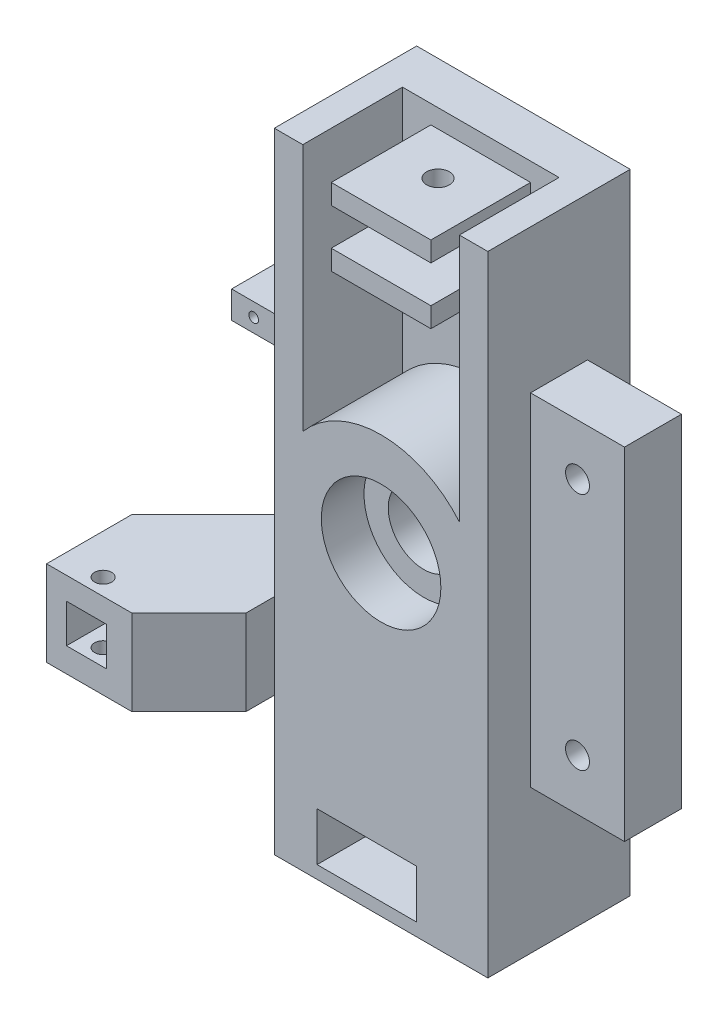
SolidWorks part; units mm, degrees
ref_plane "Front Plane" through (0, 0, 0) normal (0, 0, 1) x (1, 0, 0)
ref_plane "Top Plane" through (0, 0, 0) normal (0, 1, 0) x (1, 0, 0)
ref_plane "Right Plane" through (0, 0, 0) normal (1, 0, 0) x (0, 0, -1)
sketch "Sketch1" plane through (0, 0, 0) normal (0, 1, 0) x (1, 0, 0)
  line L1 (-37.5, -25) -> (37.5, -25)
  line L2 (-37.5, -25) -> (-37.5, 25)
  line L3 (-37.5, 25) -> (37.5, 25)
  line L4 (37.5, -25) -> (37.5, 25)
  line L5 (-37.5, -25) -> (37.5, 25) construction
  line L6 (-37.5, 25) -> (37.5, -25) construction
  point P0 (0, 0)
  dimension "D1" = 50
  dimension "D2" = 75
extrude "BE - main upright body" add sketch "Sketch1" along normal blind 221 contours L3 L4 L1 L2
sketch "Sketch2" plane through (0, 0, 25) normal (0, 0, 1) x (1, 0, 0)
  line L0 (-37.5, 221) -> (37.5, 0) construction
  line L1 (-37.5, 0) -> (37.5, 221) construction
  circle A0 centre (0, 110.5) radius 21
  point P10 (0, 110.5)
  dimension "D1" = 42
sketch "Sketch3" plane through (0, 0, -25) normal (0, 0, -1) x (-1, 0, 0)
  line L0 (-37.5, 0) -> (37.5, 221) construction
  line L1 (-37.5, 221) -> (37.5, 0) construction
  circle A0 centre (0, 110.5) radius 23.5
  point P10 (0, 110.5)
  dimension "D1" = 47
sketch "Sketch4" plane through (0, 0, 25) normal (0, 0, 1) x (1, 0, 0)
  line L0 (-37.5, 221) -> (37.5, 0) construction
  line L1 (37.5, 221) -> (-37.5, 0) construction
  line L2 (-37.5, 0) -> (37.5, 0) construction
  circle A0 centre (0, 110.5) radius 12.5
  dimension "D1" = 25
extrude "CE - Through hole" cut sketch "Sketch4" against normal through all
extrude "CE - Inner bearing" cut sketch "Sketch2" against normal blind 15 contours A0
extrude "CE - Outer bearing" cut sketch "Sketch3" against normal blind 15 contours A0
sketch "Sketch7" plane through (37.5, 0, 0) normal (1, 0, 0) x (0, 0, -1)
  line L0 (25, 221) -> (25, 0) construction
  line L1 (-10, 50.5) -> (10, 50.5)
  line L2 (-10, 50.5) -> (-10, 170.5)
  line L3 (-10, 170.5) -> (10, 170.5)
  line L4 (10, 50.5) -> (10, 170.5)
  line L5 (-10, 50.5) -> (10, 170.5) construction
  line L6 (-10, 170.5) -> (10, 50.5) construction
  line L7 (-25, 110.5) -> (25, 110.5) construction
  line L8 (-25, 221) -> (-25, 0) construction
  point P0 (0, 110.5)
  point P12 (0, 110.5)
  dimension "D1" = 120
  dimension "D2" = 20
extrude "BE - caliper mount" add sketch "Sketch7" along normal blind 33
sketch "Sketch21" plane through (0, 0, 0) normal (0, 0, 1) x (1, 0, 0)
  line L1 (-67.5, 140.0208) -> (-37.5, 140.0208)
  line L2 (-67.5, 140.0208) -> (-67.5, 149.6028)
  line L3 (-67.5, 149.6028) -> (-37.5, 149.6028)
  line L4 (-37.5, 140.0208) -> (-37.5, 149.6028)
  line L5 (-67.5, 140.0208) -> (-37.5, 149.6028) construction
  line L6 (-67.5, 149.6028) -> (-37.5, 140.0208) construction
  line L7 (-37.5, 221) -> (-37.5, 0) construction
  point P0 (-52.5, 144.8118)
  dimension "D1" = 30
extrude "BE - temp sensor mount v2" add sketch "Sketch21" along normal mid plane 20
sketch "Sketch8" [suppressed] plane through (-37.5, 0, 0) normal (-1, 0, 0) x (0, 0, 1)
  line L0 (0, 221) -> (0, 148.4522) construction
  line L1 (-10.7205, 138.4522) -> (10.7205, 138.4522)
  line L2 (-10.7205, 138.4522) -> (-10.7205, 158.4522)
  line L3 (-10.7205, 158.4522) -> (10.7205, 158.4522)
  line L4 (10.7205, 138.4522) -> (10.7205, 158.4522)
  line L5 (-10.7205, 138.4522) -> (10.7205, 158.4522) construction
  line L6 (-10.7205, 158.4522) -> (10.7205, 138.4522) construction
  line L7 (25, 221) -> (-25, 221) construction
  point P0 (0, 148.4522)
  dimension "D1" = 20
extrude "BE - temp sensor mount" [suppressed] add sketch "Sketch8" along normal blind 50
sketch "Sketch9" plane through (-37.5, 0, 0) normal (-1, 0, 0) x (0, 0, 1)
  line L0 (25, 89.5) -> (25, 131.5) construction
  line L1 (-5, 48.5) -> (55, 48.5)
  line L2 (-5, 48.5) -> (-5, 78.5)
  line L3 (-5, 78.5) -> (55, 78.5)
  line L4 (55, 48.5) -> (55, 78.5)
  line L5 (-5, 48.5) -> (55, 78.5) construction
  line L6 (-5, 78.5) -> (55, 48.5) construction
  line L7 (25, 89.5) -> (25, 131.5) construction
  line L8 (25, 221) -> (25, 0) construction
  point P0 (25, 63.5)
  point P7 (25, 110.5)
  dimension "D1" = 47
  dimension "D2" = 60
  dimension "D3" = 30
extrude "BE - tie rod mount" add sketch "Sketch9" along normal blind 50
sketch "Sketch10" plane through (0, 0, 10) normal (0, 0, 1) x (1, 0, 0)
  line L0 (54, 170.5) -> (54, 50.5) construction
  line L1 (70.5, 170.5) -> (37.5, 170.5) construction
  line L2 (70.5, 50.5) -> (37.5, 50.5) construction
  line L3 (54, 152.5) -> (54, 68.5) construction
  circle A0 centre (54, 152.5) radius 4.2
  circle A1 centre (54, 68.5) radius 4.2
  point P10 (54, 110.5)
  point P20 (54, 152.5)
  dimension "D1" = 8.4
  dimension "D2" = 84
extrude "CE - caliper holes" cut sketch "Sketch10" against normal through all
sketch "Sketch12" plane through (0, 0, 25) normal (0, 0, 1) x (1, 0, 0)
  line L0 (-12.5, 201) -> (12.5, 201) construction
  line L2 (-37.5, 221) -> (37.5, 221) construction
  circle A0 centre (-12.5, 201) radius 4
  circle A1 centre (12.5, 201) radius 4
  point P2 (0, 201)
  dimension "D1" = 8
  dimension "D2" = 20
  dimension "D3" = 25
extrude "CE - top clevis holes" cut sketch "Sketch12" against normal through all
sketch "Sketch13" plane through (0, 0, 25) normal (0, 0, 1) x (1, 0, 0)
  line L2 (-27.5, 133.7325) -> (-27.5, 221)
  line L3 (-27.5, 221) -> (27.5, 221)
  line L4 (27.5, 133.7325) -> (27.5, 221)
  line L5 (-27.5, 221) -> (27.5, 133.7325) construction
  line L6 (-27.5, 133.7325) -> (27.5, 221) construction
  line L7 (-37.5, 221) -> (37.5, 221) construction
  line L8 (-12.5, 201) -> (12.5, 201) construction
  arc A2 (27.5, 133.7325) -> (-27.5, 133.7325) centre (0, 110.5) ccw
  circle A4 centre (0, 110.5) radius 21 construction
  circle A6 centre (12.5, 201) radius 4 construction
  circle A7 centre (-12.5, 201) radius 4 construction
  circle A8 centre (12.5, 201) radius 4 construction
  circle A9 centre (-12.5, 201) radius 4 construction
  point P0 (0, 177.3663)
  point P13 (12.5, 201.4098)
  point P14 (-12.5, 201)
  point P15 (0, 201)
  point P16 (-4.3194, 201)
  point P20 (-12.9711, 201)
  point P23 (0, 0)
  dimension "D2" = 55
  dimension "D1" = 15
extrude "CE - top clevis space" cut sketch "Sketch13" against normal blind 35 contours L3 L4 A2 L2
ref_plane "Top clevis plane" through (0, 0, 5) normal (0, 0, 1) x (1, 0, 0)
sketch "Sketch23" plane through (0, 0, -10) normal (0, 0, 1) x (1, 0, 0)
  line L0 (0, 211) -> (0, 201) construction
  line L1 (-17.5, 214.5) -> (17.5, 214.5)
  line L2 (-17.5, 214.5) -> (-17.5, 207.5)
  line L3 (-17.5, 207.5) -> (17.5, 207.5)
  line L4 (17.5, 214.5) -> (17.5, 207.5)
  line L5 (-17.5, 214.5) -> (17.5, 207.5) construction
  line L6 (-17.5, 207.5) -> (17.5, 214.5) construction
  line L7 (-17.5, 187.5) -> (17.5, 187.5)
  line L8 (-17.5, 187.5) -> (-17.5, 194.5)
  line L9 (-17.5, 194.5) -> (17.5, 194.5)
  line L10 (17.5, 187.5) -> (17.5, 194.5)
  line L11 (-17.5, 187.5) -> (17.5, 194.5) construction
  line L12 (-17.5, 194.5) -> (17.5, 187.5) construction
  line L13 (0, 201) -> (0, 191) construction
  point P0 (0, 211)
  point P5 (0, 191)
  point P10 (0, 211.6073)
  point P11 (0, 201)
  point P17 (0, 0)
  dimension "D1" = 7
  dimension "D2" = 10
  dimension "D3" = 35
extrude "Boss-Extrude1" add sketch "Sketch23" along normal up to surface (35 mm away) contours L1 L4 L3 L2 | L7 L10 L9 L8 up to face at (21, 110.5, 25)
ref_point "Position of Top Clevis"
sketch "Sketch24" plane through (0, 214.5, 0) normal (0, 1, 0) x (1, 0, 0)
  circle A0 centre (0, -5) radius 4
  point P2 (0, -5)
  point P4 (0, -5)
  dimension "D1" = 8
extrude "Cut-Extrude5" cut sketch "Sketch24" against normal up to surface (27 mm away) up to face at (0, 187.5, 7.5)
sketch "Sketch14" plane through (0, 0, 25) normal (0, 0, 1) x (1, 0, 0)
  line L1 (-22.48, 4.5) -> (2.52, 4.5)
  line L2 (-22.48, 4.5) -> (-22.48, 16.5)
  line L3 (-22.48, 16.5) -> (2.52, 16.5)
  line L4 (2.52, 4.5) -> (2.52, 16.5)
  line L5 (-22.48, 4.5) -> (2.52, 16.5) construction
  line L6 (-22.48, 16.5) -> (2.52, 4.5) construction
  point P0 (-9.98, 10.5)
  point P5 (0, 201)
  point P8 (0, 0)
  point P10 (-34.7329, 211.9212)
  dimension "D3" = 12
  dimension "D4" = 25
  dimension "D1" = 190.5
  dimension "D2" = 9.98
extrude "CE - bottom clevis space" cut sketch "Sketch14" against normal through all
ref_plane "Bottom Clevis Plane" through (0, 0, -1.65) normal (0, 0, 1) x (1, 0, 0)
ref_point "Position of Bottom Clevis"
sketch "Sketch15" plane through (0, 0, 25) normal (0, 0, 1) x (1, 0, 0)
  line L0 (2.52, 4.5) -> (2.52, 16.5) construction
  line L1 (-22.48, 16.5) -> (2.52, 16.5)
  line L2 (-22.48, 16.5) -> (-22.48, 21.5)
  line L3 (-22.48, 21.5) -> (2.52, 21.5)
  line L4 (2.52, 16.5) -> (2.52, 21.5)
  dimension "D1" = 5
extrude "CE - expand bottom clevis" cut sketch "Sketch15" against normal through all
ref_plane "P - front of part" through (2.52, 4.5, 25) normal (0, 0, 1) x (1, 0, 0)
sketch "Sketch16" plane through (2.52, 4.5, 25) normal (0, 0, 1) x (1, 0, 0)
  line L0 (0, 17) -> (-25, 17) construction
  line L1 (0, 0) -> (10.0076, 0)
  line L2 (0, 0) -> (0, 17)
  line L3 (0, 17) -> (10.0076, 17)
  line L4 (10.0076, 0) -> (10.0076, 17)
  dimension "D1" = 10.0076
extrude "CE - widen bottom clevis" cut sketch "Sketch16" against normal through all and the other way through all
chamfer "Chamfer1" distance 30 angle 45 1 edges at (-87.5, 63.5, -5)
ref_plane "P - xy plane containing bottom clevis" through (0, 10.5, 0) normal (0, 1, 0) x (1, 0, 0)
ref_plane "P - xy plane containing tie rod" through (0, 63.84, 0) normal (0, 1, 0) x (1, 0, 0)
sketch "Sketch17" plane through (0, 63.84, 0) normal (0, 1, 0) x (1, 0, 0)
  point P0 (-73.48, -49.15)
  point P1 (-9.98, 1.65)
  point P3 (-9.98, 1.65)
  dimension "D1" = 63.5
  dimension "D2" = 50.8
ref_point "Position of Tie Rod"
sketch "Sketch18" plane through (0, 0, 55) normal (0, 0, 1) x (1, 0, 0)
  line L1 (-80.502, 57.0586) -> (-66.458, 57.0586)
  line L2 (-80.502, 57.0586) -> (-80.502, 70.6214)
  line L3 (-80.502, 70.6214) -> (-66.458, 70.6214)
  line L4 (-66.458, 57.0586) -> (-66.458, 70.6214)
  line L5 (-80.502, 57.0586) -> (-66.458, 70.6214) construction
  line L6 (-80.502, 70.6214) -> (-66.458, 57.0586) construction
  point P0 (-73.48, 63.84)
  point P2 (-73.48, 63.84)
extrude "Cut-Extrude1" cut sketch "Sketch18" against normal blind 20
sketch "Sketch19" plane through (0, 78.5, 0) normal (0, 1, 0) x (1, 0, 0)
  circle A0 centre (-73.48, -49.15) radius 3
  point P2 (-73.48, -49.15)
  dimension "D1" = 6
extrude "Cut-Extrude2" cut sketch "Sketch19" against normal through all
sketch "Sketch20" [suppressed] plane through (0, 0, 10.7205) normal (0, 0, 1) x (1, 0, 0)
  line L0 (-87.5, 148.4522) -> (-37.5, 148.4522) construction
  line L1 (-87.5, 138.4522) -> (-87.5, 158.4522) construction
  line L2 (-37.5, 138.4522) -> (-37.5, 158.4522) construction
  line L3 (-87.5, 158.4522) -> (-87.5, 138.4522) construction
  line L4 (-53.5026, 148.4522) -> (-71.4974, 148.4522) construction
  circle A0 centre (-53.5026, 148.4522) radius 4
  circle A1 centre (-71.4974, 148.4522) radius 4
  point P10 (-62.5, 148.4522)
  point P16 (-53.5026, 148.4522)
  dimension "D1" = 8
extrude "Cut-Extrude3" [suppressed] cut sketch "Sketch20" against normal through all contours A0 | A1
chamfer "Chamfer2" distance 20 angle 45 1 edges at (-37.5, 63.5, 55)
sketch "Sketch22" plane through (0, 0, 10) normal (0, 0, 1) x (1, 0, 0)
  line L0 (-67.5, 144.8118) -> (-37.5, 144.8118) construction
  line L1 (-67.5, 149.6028) -> (-67.5, 140.0208) construction
  line L2 (-37.5, 140.0208) -> (-37.5, 149.6028) construction
  circle A0 centre (-59.7524, 144.8118) radius 1.7
  circle A1 centre (-49.7524, 144.8118) radius 1.7
  dimension "D2" = 3.4
  dimension "D1" = 10
extrude "Cut-Extrude4" cut sketch "Sketch22" against normal blind 20
equation "\"clevis_pin_y\"=20"
equation "\"D2@Sketch12\"=\"clevis_pin_y\""
equation "\"clevis_pin_dist\"=25"
equation "\"D3@Sketch12\"=\"clevis_pin_dist\""
equation "\"D2@Sketch13\"=\"clevis_pin_dist\" + 30"
equation "\"x_dist_a_arms\"=9.98"
equation "\"y_dist_a_arms\"=190.5"
equation "\"y_dist_bottom_clevis_to_tie_rod\"= 53.34"
equation "\"x_dist_bottom_clevis_to_tie_rod\"= 63.50"
equation "\"z_dist_bottom_clevis_to_tie_rod\"= 50.80"
equation "\"D1@Sketch14\"=\"y_dist_a_arms\""
equation "\"D2@Sketch14\"=\"x_dist_a_arms\""
